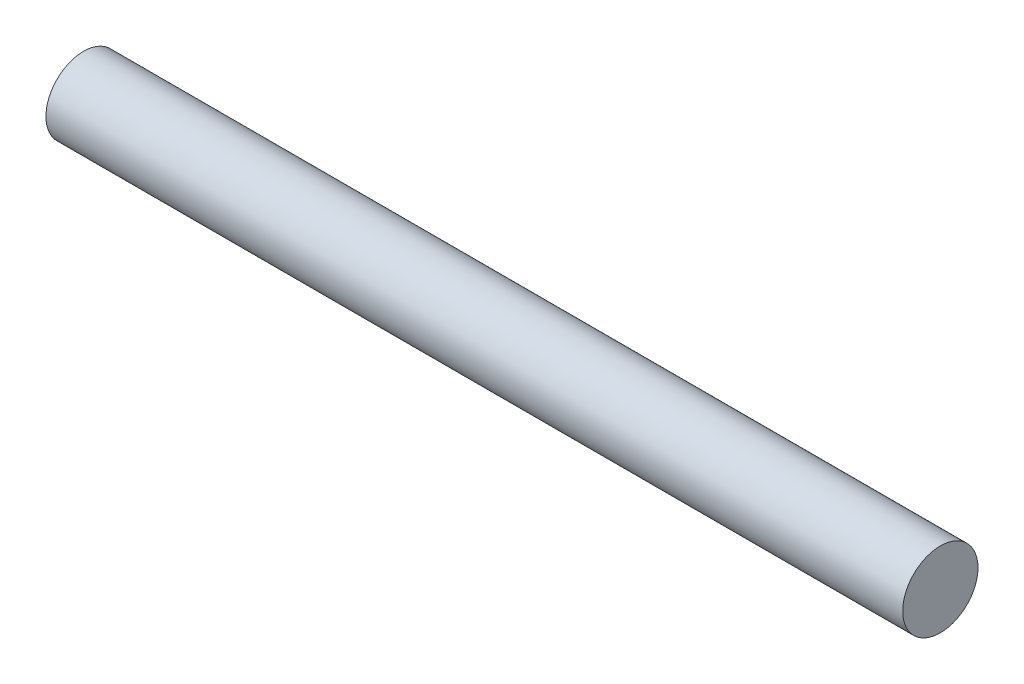
SolidWorks part; units mm, degrees
ref_plane "Front Plane" through (0, 0, 0) normal (0, 0, 1) x (1, 0, 0)
ref_plane "Top Plane" through (0, 0, 0) normal (0, 1, 0) x (1, 0, 0)
ref_plane "Right Plane" through (0, 0, 0) normal (1, 0, 0) x (0, 0, -1)
sketch "Sketch1" plane through (0, 0, 0) normal (1, 0, 0) x (0, 0, -1)
  circle A0 centre (0, 0) radius 25.4
  dimension "D1" = 50.8
extrude "Boss-Extrude1" add sketch "Sketch1" along normal blind 577.85
